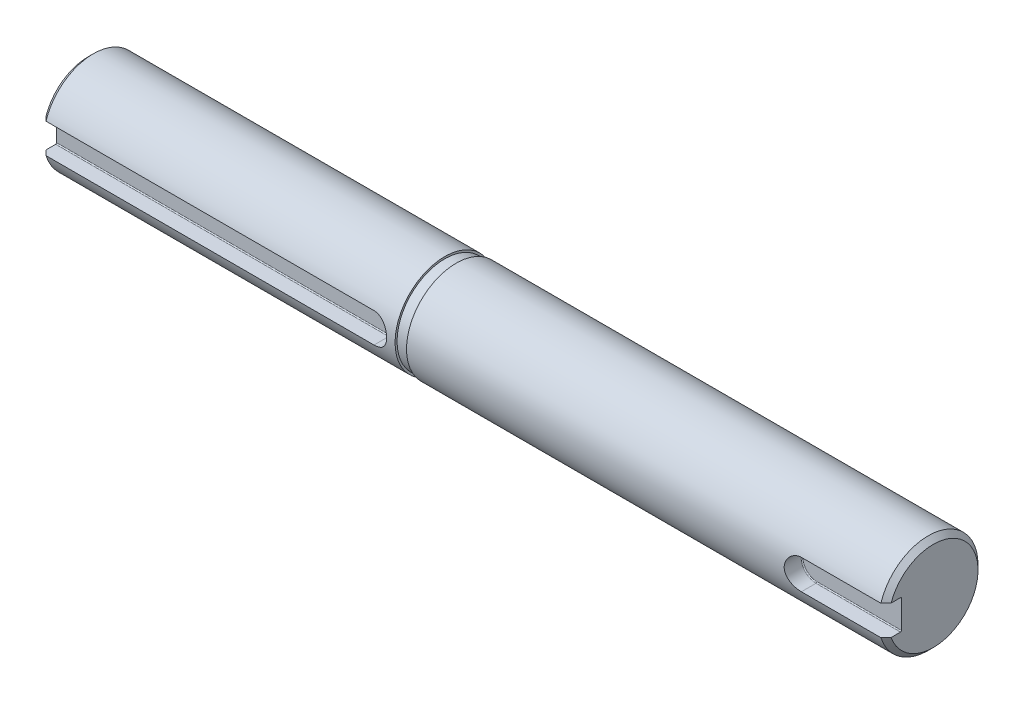
SolidWorks part; units mm, degrees
ref_plane "Front Plane" through (0, 0, 0) normal (0, 0, 1) x (1, 0, 0)
ref_plane "Top Plane" through (0, 0, 0) normal (0, 1, 0) x (1, 0, 0)
ref_plane "Right Plane" through (0, 0, 0) normal (1, 0, 0) x (0, 0, -1)
sketch "Sketch1" plane through (0, 0, 0) normal (0, 0, 1) x (1, 0, 0)
  line L0 (0, 0) -> (85, 0) construction
  line L1 (0, 0) -> (85, 0)
  line L2 (85, 0) -> (85, 5)
  line L3 (85, 5) -> (0, 5)
  line L4 (0, 5) -> (0, 0)
  dimension "L" = 85
  dimension "D" = 10
revolve "Revolve1" add sketch "Sketch1" angle 360 about L0
chamfer "Chamfer1" distance 0.5 angle 45 2 edges at (85, 0, 5) (0, 0, 5)
ref_plane "Plane1" through (0, 0, 5) normal (0, 0, 1) x (1, 0, 0)
ref_plane "Plane2" through (85, 0, 0) normal (1, 0, 0) x (0, 0, -1)
other "DeleteFace1" [suppressed]
chamfer "Chamfer2" [suppressed] distance 2 angle 45
ref_plane "Dim. KC" [suppressed] through (2, 0, 0) normal (1, 0, 0) x (0, 0, -1)
ref_plane "Plane3" [suppressed] through (2, 0, 0) normal (1, 0, 0) x (0, 0, -1)
ref_plane "Plane4" [suppressed] through (8, 0, 0) normal (1, 0, 0) x (0, 0, -1)
sketch "Sketch2" [suppressed] plane through (0, 0, 4) normal (0, 0, 1) x (1, 0, 0)
  line L0 (2, 0) -> (8, 0) construction
  line L1 (2, 1.5) -> (8, 1.5)
  line L2 (2, 1.5) -> (2, -1.5) construction
  line L3 (2, -1.5) -> (8, -1.5)
  line L4 (8, 1.5) -> (8, -1.5) construction
  line L5 (5, 1.5) -> (5, -1.5) construction
  line L6 (2, -4.4) -> (2, 4.4) construction
  line L7 (8, 1.5) -> (8, -1.5)
  line L8 (8, -4.4) -> (8, 4.4) construction
  line L9 (2, 1.5) -> (2, -1.5)
  line L12 (2, -4.4) -> (2, 4.4) construction
  dimension "A" = 10
  dimension "B_s" = 3
extrude "Boss-Extrude1" [suppressed] add sketch "Sketch2" against normal blind 1.8 separate body
fillet "Fillet1" [suppressed] type full round
fillet "Fillet2" [suppressed] type full round
sketch "Sketch3" [suppressed] plane through (0, 0, 4) normal (0, 0, 1) x (1, 0, 0)
  line L0 (9, 1.5) -> (9, -1.5) construction
  line L1 (6.5, 1.5) -> (11.5, 1.5)
  line L2 (6.5, 1.5) -> (6.5, -1.5)
  line L3 (6.5, -1.5) -> (11.5, -1.5)
  line L4 (11.5, 1.5) -> (11.5, -1.5)
  line L7 (6.5, 0) -> (11.5, 0) construction
  line L9 (10, 1.5) -> (10, -1.5) construction
  line L10 (8, 1.5) -> (8, -1.5) construction
  line L11 (2, 1.5) -> (8, 1.5) construction
  line L12 (2, -1.5) -> (8, -1.5) construction
  dimension "D1" = 1.5
  dimension "D2" = 2
  dimension "D3" = 1.5
extrude "Boss-Extrude2" [suppressed] add sketch "Sketch3" against normal blind 1.8
fillet "Fillet3" [suppressed] radius 0.1
other "DeleteFace2" [suppressed]
other "DeleteFace3" [suppressed]
combine bodies "Combine1" [suppressed] operation type subtract main body 101 bodies to subtract 146
ref_plane "KC_SEC1" [suppressed] through (5, 0, 0) normal (1, 0, 0) x (0, 0, -1)
ref_plane "KC_SEC2" [suppressed] through (9, 0, 0) normal (1, 0, 0) x (0, 0, -1)
ref_plane "Dim. WKC" through (0, 0, 0) normal (1, 0, 0) x (0, 0, -1)
ref_plane "Dim. K" through (85, 0, 0) normal (1, 0, 0) x (0, 0, -1)
ref_plane "Plane5" through (0, 0, 0) normal (1, 0, 0) x (0, 0, -1)
ref_plane "Plane6" through (85, 0, 0) normal (1, 0, 0) x (0, 0, -1)
sketch "Sketch4" plane through (0, 0, 5) normal (0, 0, 1) x (1, 0, 0)
  line L0 (0, 1.5) -> (0, -1.5)
  line L1 (0, 1.5) -> (35, 1.5)
  line L2 (0, 1.5) -> (0, -1.5) construction
  line L3 (0, -1.5) -> (35, -1.5)
  line L4 (35, 1.5) -> (35, -1.5)
  line L5 (0, -4.4) -> (0, 4.4) construction
  line L6 (0, -3.3) -> (0, 3.3) construction
  line L7 (35, 0) -> (0, 0) construction
  line L8 (17.5, 1.5) -> (17.5, -1.5) construction
  dimension "B_s" = 3
  dimension "C" = 35
extrude "Boss-Extrude3" add sketch "Sketch4" against normal blind 1.8 separate body
sketch "Sketch5" plane through (0, 0, 5) normal (0, 0, 1) x (1, 0, 0)
  line L0 (0, 0) -> (85, 0) construction
  line L2 (85, -3.3) -> (85, 3.3) construction
  line L4 (85, -3.3) -> (85, 3.3) construction
  line L5 (80, 1.5) -> (80, -1.5) construction
  line L9 (75, 1.5) -> (85, 1.5)
  line L10 (75, 1.5) -> (75, -1.5)
  line L11 (75, -1.5) -> (85, -1.5)
  line L12 (85, 1.5) -> (85, -1.5) construction
  line L13 (85, 1.5) -> (85, -1.5)
  dimension "B_s" = 3
  dimension "E" = 10
extrude "Boss-Extrude4" add sketch "Sketch5" against normal blind 1.8 separate body
sketch "Sketch6" plane through (0, 0, 5) normal (0, 0, 1) x (1, 0, 0)
  line L0 (0, 1.5) -> (35, 1.5) construction
  line L1 (33.5, 1.5) -> (38.5, 1.5)
  line L2 (33.5, 1.5) -> (33.5, -1.5)
  line L3 (33.5, -1.5) -> (38.5, -1.5)
  line L4 (38.5, 1.5) -> (38.5, -1.5)
  line L5 (0, -1.5) -> (35, -1.5) construction
  line L6 (35, 1.5) -> (35, -1.5) construction
  line L7 (36, 1.5) -> (36, -1.5) construction
  line L8 (37, 1.5) -> (37, -1.5) construction
  dimension "D1" = 1.5
  dimension "D2" = 2
  dimension "D3" = 1.5
extrude "Boss-Extrude5" [suppressed] add sketch "Sketch6" against normal blind 1.8
fillet "Fillet4" [suppressed] type full round
fillet "Fillet5" 2 edges at (35, 1.5, 4.1) (35, -1.5, 4.1) type full round first side face at (17.5, 1.5, 4.1) second side face at (17.5, -1.5, 4.1) middle face at (35, 0, 4.1)
fillet "Fillet6" radius 0.1 4 edges at (16.75, 1.5, 3.2) (16.75, -1.5, 3.2) (35, 0, 3.2) (0, 0, 3.2)
fillet "Fillet7" [suppressed] type full round
fillet "Fillet8" 2 edges at (75, 1.5, 4.1) (75, -1.5, 4.1) type full round first side face at (80, 1.5, 4.1) second side face at (80, -1.5, 4.1) middle face at (75, 0, 4.1)
fillet "Fillet9" radius 0.1 4 edges at (80.75, 1.5, 3.2) (75, 0, 3.2) (80.75, -1.5, 3.2) (85, 0, 3.2)
other "DeleteFace4" face at (0.0396, 0, 3.2396) and patch yes
other "DeleteFace5" face at (84.9604, 0, 3.2396) and patch yes
other "DeleteFace6" [suppressed]
other "DeleteFace7" [suppressed]
combine bodies "Combine2" operation type subtract main body 101 bodies to subtract 138 139
ref_plane "WKC_SEC1" through (17.5, 0, 0) normal (1, 0, 0) x (0, 0, -1)
ref_plane "WKC_SEC2" through (80, 0, 0) normal (1, 0, 0) x (0, 0, -1)
ref_plane "WKC_SEC3" through (36, 0, 0) normal (1, 0, 0) x (0, 0, -1)
ref_plane "Dim. KZ" [suppressed] through (2, 0, 0) normal (1, 0, 0) x (0, 0, -1)
ref_plane "Plane7" [suppressed] through (2, 0, 0) normal (1, 0, 0) x (0, 0, -1)
ref_plane "Plane8" [suppressed] through (8, 0, 0) normal (1, 0, 0) x (0, 0, -1)
sketch "Sketch7" [suppressed] plane through (0, 0, 4) normal (0, 0, 1) x (1, 0, 0)
  line L0 (0, 0) -> (8, 0) construction
  line L1 (2, 1.5) -> (8, 1.5)
  line L2 (2, 1.5) -> (2, -1.5) construction
  line L3 (2, -1.5) -> (8, -1.5)
  line L4 (8, 1.5) -> (8, -1.5) construction
  line L5 (2, -4.4) -> (2, 4.4) construction
  line L6 (2, -4.4) -> (2, 4.4) construction
  line L7 (2, 1.5) -> (2, -1.5)
  line L8 (8, 1.5) -> (8, -1.5)
  line L9 (8, -4.4) -> (8, 4.4) construction
  line L10 (5, 1.5) -> (5, -1.5) construction
  dimension "B_s" = 3
  dimension "Z" = 6
extrude "Boss-Extrude6" [suppressed] add sketch "Sketch7" against normal blind 1.8 separate body
fillet "Fillet10" [suppressed] type full round
fillet "Fillet11" [suppressed] type full round
sketch "Sketch8" [suppressed] plane through (0, 0, 4) normal (0, 0, 1) x (1, 0, 0)
  line L0 (1, 1.5) -> (1, -1.5) construction
  line L1 (-1.5, 1.5) -> (3.5, 1.5)
  line L2 (-1.5, 1.5) -> (-1.5, -1.5)
  line L3 (-1.5, -1.5) -> (3.5, -1.5)
  line L4 (3.5, 1.5) -> (3.5, -1.5)
  line L5 (2, 1.5) -> (2, -1.5) construction
  line L7 (-1.5, 0) -> (3.5, 0) construction
  line L9 (0, 1.5) -> (0, -1.5) construction
  line L10 (2, 1.5) -> (8, 1.5) construction
  line L11 (2, -1.5) -> (8, -1.5) construction
  dimension "D1" = 1.5
  dimension "D2" = 2
  dimension "D3" = 1.5
extrude "Boss-Extrude7" [suppressed] add sketch "Sketch8" against normal blind 1.8
fillet "Fillet12" [suppressed] radius 0.1
other "DeleteFace8" [suppressed]
other "DeleteFace9" [suppressed]
combine bodies "Combine3" [suppressed] operation type subtract main body 101 bodies to subtract 147
ref_plane "KZ_SEC1" [suppressed] through (5, 0, 0) normal (1, 0, 0) x (0, 0, -1)
ref_plane "KZ_SEC2" [suppressed] through (1, 0, 0) normal (1, 0, 0) x (0, 0, -1)
ref_plane "Dim. FC" [suppressed] through (1, 0, 0) normal (1, 0, 0) x (0, 0, -1)
sketch "Sketch9" [suppressed] plane through (0, 0, 0) normal (0, 1, 0) x (1, 0, 0)
  line L0 (0, 0) -> (2, 0) construction
  line L1 (1, -3) -> (2, -3)
  line L2 (1, -3) -> (1, -4)
  line L3 (1, -4) -> (2, -4)
  line L4 (2, -3) -> (2, -4)
  line L5 (1, -3.3) -> (1, 3.3) construction
  line L6 (1.5, -4) -> (1.5, -3) construction
  dimension "G" = 1
  dimension "H" = 1
  dimension "D" = 10
extrude "Cut-Extrude1" [suppressed] cut sketch "Sketch9" against normal through all and the other way through all
ref_plane "FC_SEC" [suppressed] through (1.5, 0, 0) normal (1, 0, 0) x (0, 0, -1)
ref_plane "Dim. WFC" [suppressed] through (1, 0, 0) normal (1, 0, 0) x (0, 0, -1)
ref_plane "Dim. W" [suppressed] through (19, 0, 0) normal (1, 0, 0) x (0, 0, -1)
sketch "Sketch10" [suppressed] plane through (0, 0, 0) normal (0, 1, 0) x (1, 0, 0)
  line L0 (0, 0) -> (19, 0) construction
  line L1 (1, -4) -> (2, -4)
  line L2 (1, -4) -> (1, -3)
  line L3 (1, -3) -> (2, -3)
  line L4 (2, -4) -> (2, -3)
  line L5 (1.5, -3) -> (1.5, -4) construction
  line L6 (19, -4) -> (18, -4)
  line L7 (19, -4) -> (19, -3)
  line L8 (19, -3) -> (18, -3)
  line L9 (18, -4) -> (18, -3)
  line L10 (1, -3.3) -> (1, 3.3) construction
  line L11 (19, -3.3) -> (19, 3.3) construction
  line L12 (18.5, -3) -> (18.5, -4) construction
  dimension "J" = 1
  dimension "V" = 1
  dimension "H" = 1
  dimension "D" = 10
  dimension "H_s_R" = 1
extrude "Cut-Extrude2" [suppressed] cut sketch "Sketch10" against normal through all and the other way through all
ref_plane "WFC_SEC1" [suppressed] through (1.5, 0, 0) normal (1, 0, 0) x (0, 0, -1)
ref_plane "WFC_SEC2" [suppressed] through (18.5, 0, 0) normal (1, 0, 0) x (0, 0, -1)
ref_plane "Dim. SFC" [suppressed] through (1, 0, 0) normal (1, 0, 0) x (0, 0, -1)
sketch "Sketch11" [suppressed] plane through (0, 0, 0) normal (0, 1, 0) x (1, 0, 0)
  line L0 (0, 0) -> (2, 0) construction
  line L1 (1, -4) -> (2, -4)
  line L2 (1, -4) -> (1, -3)
  line L3 (1, -3) -> (2, -3)
  line L4 (2, -4) -> (2, -3)
  line L5 (1, -3.3) -> (1, 3.3) construction
  line L6 (1.5, -3) -> (1.5, -4) construction
  dimension "D" = 10
  dimension "SG" = 1
  dimension "H" = 1
extrude "Cut-Extrude3" [suppressed] cut sketch "Sketch11" against normal through all and the other way through all
pattern_circular "CirPattern1" [suppressed] count 2 every 120 of bodies 119
ref_plane "Plane9" [suppressed] through (0, 0, 0) normal (0, -0.5, 0.866) x (1, 0, 0)
sketch "Sketch12" [suppressed] plane through (0, 0, 0) normal (0, -0.5, 0.866) x (1, 0, 0)
  line L0 (0, 0) -> (2, 0) construction
  line L2 (1, -3) -> (2, -3)
  line L3 (1, -3) -> (1, -4)
  line L4 (1, -4) -> (2, -4)
  line L5 (2, -3) -> (2, -4)
  line L6 (1, -3.3) -> (1, 3.3) construction
  dimension "D" = 10
  dimension "SG" = 1
  dimension "H" = 1
ref_plane "SFC_SEC" [suppressed] through (1.5, 0, 0) normal (1, 0, 0) x (0, 0, -1)
sketch "Sketch13" [suppressed] plane through (1.5, 0, 0) normal (1, 0, 0) x (0, 0, -1)
  line L0 (-4, 0) -> (-3, 0) construction
  line L1 (-3, 0) -> (-4, 0) construction
  line L2 (2, -3.4641) -> (1.5, -2.5981) construction
  line L3 (1.5, -2.5981) -> (2, -3.4641) construction
  line L4 (1.5, -2.5981) -> (2, -3.4641) construction
  dimension "ANG" = 120
sketch "Sketch14" [suppressed] plane through (0, 0, 0) normal (0, 1, 0) x (1, 0, 0)
  line L0 (0, 0) -> (20, 0) construction
  line L1 (1.5, 4) -> (1.5, 3.5) construction
  line L2 (0, 3.5) -> (3, 3.5)
  line L3 (0, 3.5) -> (0, 4)
  line L4 (0, 4) -> (3, 4)
  line L5 (3, 3.5) -> (3, 4)
  line L6 (17, 3.5) -> (20, 3.5)
  line L7 (17, 3.5) -> (17, 4)
  line L8 (17, 4) -> (20, 4)
  line L9 (20, 3.5) -> (20, 4)
  line L10 (0, -4) -> (3, -4)
  line L11 (0, -4) -> (0, -3.5)
  line L12 (0, -3.5) -> (3, -3.5)
  line L13 (3, -4) -> (3, -3.5)
  line L14 (17, -4) -> (20, -4)
  line L15 (17, -4) -> (17, -3.5)
  line L16 (17, -3.5) -> (20, -3.5)
  line L17 (20, -4) -> (20, -3.5)
  line L18 (1.5, -3.5) -> (1.5, -4) construction
  line L19 (18.5, 4) -> (18.5, 3.5) construction
  line L20 (18.5, -3.5) -> (18.5, -4) construction
  dimension "D" = 10
  dimension "W_1" = 7
  dimension "KWC" = 3
  dimension "KWC_L1" = 3
  dimension "KWC_R1" = 3
  dimension "KWC_R2" = 3
  dimension "W_1_R" = 7
extrude "Cut-Extrude4" [suppressed] cut sketch "Sketch14" against normal through all and the other way through all
ref_plane "KWC_SEC1" [suppressed] through (1.5, 0, 0) normal (1, 0, 0) x (0, 0, -1)
ref_plane "KWC_SEC2" [suppressed] through (18.5, 0, 0) normal (1, 0, 0) x (0, 0, -1)
sketch "Sketch15" [suppressed] plane through (0, 0, 0) normal (0, 1, 0) x (1, 0, 0)
  line L0 (0, 0) -> (20, 0) construction
  line L1 (1.5, -3) -> (1.5, -4) construction
  line L2 (0, 3) -> (3, 3)
  line L3 (0, 3) -> (0, 4)
  line L4 (0, 4) -> (3, 4)
  line L5 (3, 3) -> (3, 4)
  line L6 (17, 3) -> (20, 3)
  line L7 (17, 3) -> (17, 4)
  line L8 (17, 4) -> (20, 4)
  line L9 (20, 3) -> (20, 4)
  line L10 (0, -4) -> (3, -4)
  line L11 (0, -4) -> (0, -3)
  line L12 (0, -3) -> (3, -3)
  line L13 (3, -4) -> (3, -3)
  line L14 (17, -4) -> (20, -4)
  line L15 (17, -4) -> (17, -3)
  line L16 (17, -3) -> (20, -3)
  line L17 (20, -4) -> (20, -3)
  line L18 (18.5, -3) -> (18.5, -4) construction
  dimension "D" = 10
  dimension "KWC_L1" = 3
  dimension "KWC_R1" = 3
  dimension "WC" = 6
  dimension "KWC" = 3
  dimension "KWC_R2" = 3
  dimension "WC_R" = 6
extrude "Cut-Extrude5" [suppressed] cut sketch "Sketch15" against normal through all and the other way through all
ref_plane "WC_SEC1" [suppressed] through (1.5, 0, 0) normal (1, 0, 0) x (0, 0, -1)
ref_plane "WC_SEC2" [suppressed] through (18.5, 0, 0) normal (1, 0, 0) x (0, 0, -1)
sketch "Sketch16" plane through (0, 0, 0) normal (0, 0, 1) x (1, 0, 0)
  line L0 (85, 5) -> (0, 5) construction
  line L1 (35.85, 4.8) -> (37, 4.8)
  line L2 (35.85, 4.8) -> (35.85, 5)
  line L3 (35.85, 5) -> (37, 5)
  line L4 (37, 4.8) -> (37, 5)
  line L5 (0, 0) -> (37, 0) construction
  line L6 (0, 5) -> (0, 0) construction
  dimension "D_s_1" = 9.6
  dimension "M_s" = 1.15
  dimension "TA" = 37
revolve "Cut-Revolve1" cut sketch "Sketch16" angle 360 about L5
sketch "Sketch17" [suppressed] plane through (0, 0, 0) normal (0, 0, 1) x (1, 0, 0)
  line L1 (21.85, 4.8) -> (23, 4.8)
  line L2 (21.85, 4.8) -> (21.85, 5)
  line L3 (21.85, 5) -> (23, 5)
  line L4 (23, 4.8) -> (23, 5)
  line L5 (0, 0) -> (50, 0) construction
  line L7 (50, -3.3) -> (50, 3.3) construction
  dimension "D_s_1" = 9.6
  dimension "M_s" = 1.15
  dimension "D" = 10
  dimension "TB" = 28.15
revolve "Cut-Revolve2" [suppressed] cut sketch "Sketch17" angle 360 about L5
sketch "Sketch18" [suppressed] plane through (0, 0, 0) normal (0, 0, 1) x (1, 0, 0)
  line L0 (0, 0) -> (20, 0) construction
  line L1 (0, 4) -> (0, -4) construction
  line L3 (1, 4) -> (5, 4)
  line L4 (1, 4) -> (1, 3.5)
  line L5 (1, 3.5) -> (5, 3.5)
  line L6 (5, 4) -> (5, 3.5)
  line L7 (20, 4) -> (0, 4) construction
  line L8 (20, -3.3) -> (20, 3.3) construction
  dimension "D_s_2" = 7
  dimension "UC" = 1
  dimension "L1_s" = 4
revolve "Cut-Revolve3" [suppressed] cut sketch "Sketch18" angle 360 about L0
ref_plane "Dim. SC" [suppressed] through (2, 0, 0) normal (1, 0, 0) x (0, 0, -1)
sketch "Sketch19" [suppressed] plane through (0, 0, 0) normal (0, 1, 0) x (1, 0, 0)
  line L0 (20, -3.3) -> (20, 3.3) construction
  line L1 (2, -3.5) -> (10, -3.5)
  line L2 (2, -3.5) -> (2, -4)
  line L3 (2, -4) -> (10, -4)
  line L4 (10, -3.5) -> (10, -4)
  line L5 (2, 4) -> (10, 4)
  line L6 (2, 4) -> (2, 3.5)
  line L7 (2, 3.5) -> (10, 3.5)
  line L8 (10, 4) -> (10, 3.5)
  line L9 (6, 4) -> (6, 3.5) construction
  line L10 (6, -3.5) -> (6, -4) construction
  line L12 (0, 0) -> (20, 0) construction
  line L14 (2, -3.3) -> (2, 3.3) construction
  dimension "W_2" = 7
  dimension "L2_s" = 8
  dimension "D" = 10
  dimension "L2_s_L1" = 8
extrude "Cut-Extrude6" [suppressed] cut sketch "Sketch19" against normal through all and the other way through all
ref_plane "SC_SEC" [suppressed] through (6, 0, 0) normal (1, 0, 0) x (0, 0, -1)
equation "\"Plane dim\"= \"D@Sketch1\" * 0.5"
equation "\"D1@Plane3\"= if ( \"KC@Dim. KC\" < 1 , 0 , \"KC@Dim. KC\" )"
equation "\"D1@Plane4\" = if ( \"KC@Dim. KC\" > \"L@Sketch1\" - \"A@Sketch2\" - 1 , \"L@Sketch1\" , \"KC@Dim. KC\" + \"A@Sketch2\" )"
equation "\"D1@Plane5\"=if ( \"WKC@Dim. WKC\" < 1 , 0 , \"WKC@Dim. WKC\" )"
equation "\"D1@Plane6\"=if ( \"K@Dim. K\" < 1 , 0 , \"K@Dim. K\" )"
equation "\"D1@Plane7\"=if ( \"KZ@Dim. KZ\" < 1 , 0 , \"KZ@Dim. KZ\" )"
equation "\"D1@Plane8\"=if ( \"KZ@Dim. KZ\" > \"L@Sketch1\" - \"Z@Sketch7\" - 1 , \"L@Sketch1\", \"KZ@Dim. KZ\" + \"Z@Sketch7\" )"
equation "\"D1@Sketch3\"=\"B_s@Sketch2\"/2"
equation "\"D3@Sketch3\"=\"B_s@Sketch2\"/2"
equation "\"D1@Sketch8\"=\"B_s@Sketch7\"/2"
equation "\"D3@Sketch8\"=\"B_s@Sketch7\"/2"
equation "\"D1@Sketch6\"=\"B_s@Sketch4\"/2"
equation "\"D3@Sketch6\"=\"B_s@Sketch4\"/2"
equation "\"D@Sketch12\" = \"D@Sketch11\""
equation "\"SG@Sketch12\" = \"SG@Sketch11\""
equation "\"H@Sketch12\"= \"H@Sketch11\""
